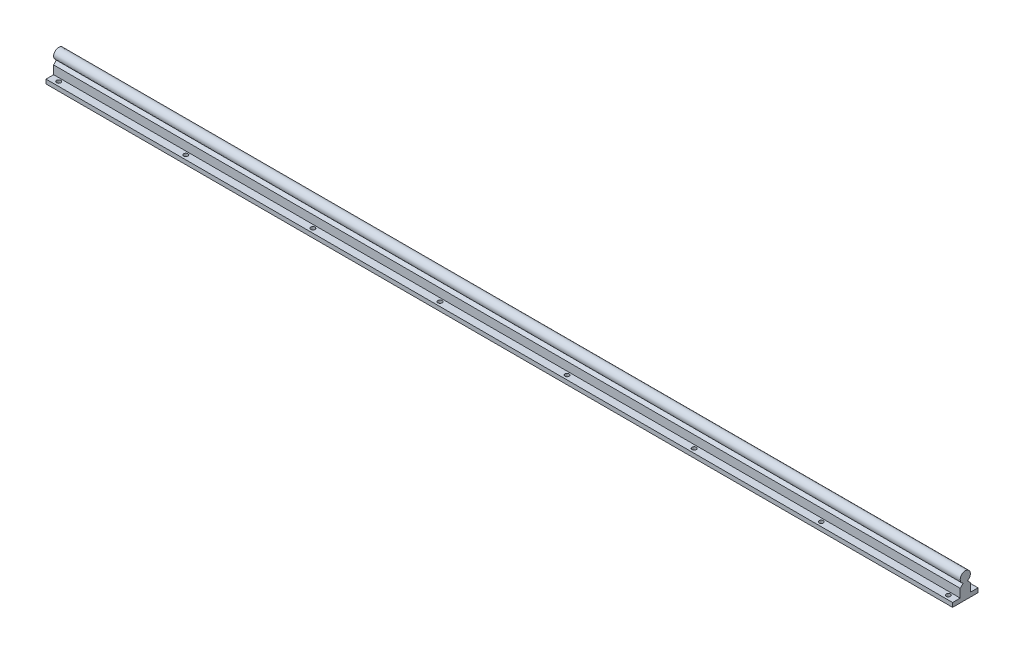
SolidWorks part; units mm, degrees
ref_plane "Спереди" through (0, 0, 0) normal (0, 0, 1) x (1, 0, 0)
ref_plane "Сверху" through (0, 0, 0) normal (0, 1, 0) x (1, 0, 0)
ref_plane "Справа" through (0, 0, 0) normal (1, 0, 0) x (0, 0, -1)
sketch "Эскиз1" plane through (0, 0, 0) normal (1, 0, 0) x (0, 0, -1)
  line L0 (-6, 15) -> (-2.5, 18.5456)
  line L1 (-15, 5) -> (-6, 5)
  line L2 (-15, 5) -> (-15, 0)
  line L3 (-15, 0) -> (15, 0)
  line L4 (15, 5) -> (15, 0)
  line L6 (-15, 2.5) -> (15, 2.5) construction
  line L8 (-6, 15) -> (-6, 5)
  line L10 (6, 15) -> (6, 5)
  line L11 (0, 0) -> (0, 18) construction
  line L13 (6, 15) -> (2.5, 18.5456)
  line L14 (6, 5) -> (15, 5)
  arc A0 (2.5, 18.5456) -> (-2.5, 18.5456) centre (0, 24) ccw
  dimension "D5" = 12
  dimension "D6" = 30
  dimension "D1" = 5
  dimension "D2" = 30
  dimension "D3" = 12
  dimension "D4" = 5
  dimension "D7" = 10
extrude "Бобышка-Вытянуть1" add sketch "Эскиз1" against normal mid plane 1070
sketch "Эскиз2" plane through (0, 0, 0) normal (0, -1, 0) x (1, 0, 0)
  line L0 (0, 0) -> (-70.8439, 0) construction
  line L1 (-535, 15) -> (-535, -15) construction
  circle A0 centre (-525, 10) radius 2.5
  circle A1 centre (-525, -10) radius 2.5
  dimension "D1" = 5
  dimension "D2" = 20
  dimension "D3" = 10
extrude "Вырез-Вытянуть1" cut sketch "Эскиз2" against normal blind 1070
pattern_linear "Линейный массив1" count 8 spacing 150 along (1, 0, 0) of "Вырез-Вытянуть1"
